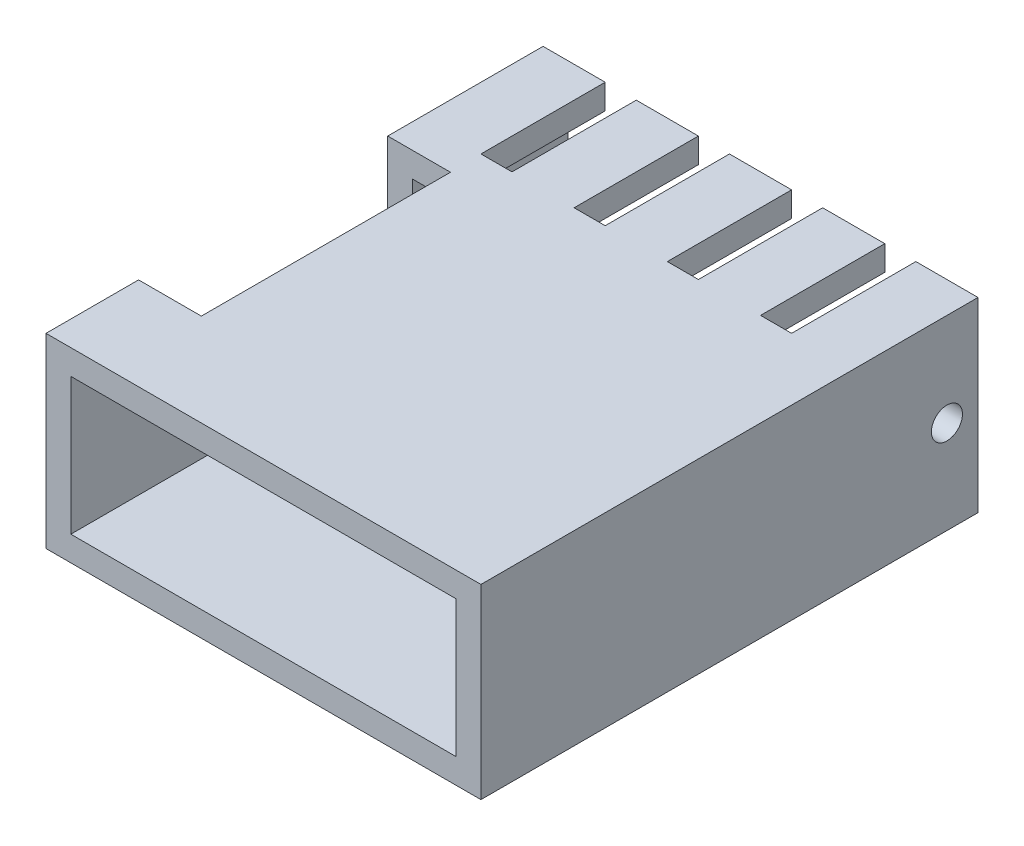
SolidWorks part; units mm, degrees
ref_plane "Front Plane" through (0, 0, 0) normal (0, 0, 1) x (1, 0, 0)
ref_plane "Top Plane" through (0, 0, 0) normal (0, 1, 0) x (1, 0, 0)
ref_plane "Right Plane" through (0, 0, 0) normal (1, 0, 0) x (0, 0, -1)
sketch "Sketch1" plane through (0, 0, 0) normal (0, 1, 0) x (1, 0, 0)
  line L1 (0, 0) -> (88.9, 0)
  line L2 (0, 0) -> (0, 101.6)
  line L3 (0, 101.6) -> (88.9, 101.6)
  line L4 (88.9, 0) -> (88.9, 101.6)
  dimension "D1" = 101.6
  dimension "D2" = 88.9
extrude "Boss-Extrude1" add sketch "Sketch1" along normal blind 38.1 contours L1 L4 L3 L2
shell "Shell1" thickness 5.08 removed face at (44.45, 19.05, -101.6) removed face at (44.45, 19.05, 0)
sketch "Sketch4" plane through (0, 0, 0) normal (0, -1, 0) x (1, 0, 0)
  line L0 (0, 0) -> (0, -101.6) construction
  line L1 (0, -18.923) -> (12.827, -18.923)
  line L2 (0, -18.923) -> (0, -69.85)
  line L3 (0, -69.85) -> (12.827, -69.85)
  line L4 (12.827, -18.923) -> (12.827, -69.85)
  line L5 (0, -101.6) -> (88.9, -101.6) construction
  point P5 (0, 0)
  point P10 (12.827, -25.273)
  dimension "D1" = 50.927
  dimension "D2" = 12.827
  dimension "D3" = 31.75
extrude "Cut-Extrude3" cut sketch "Sketch4" against normal through all from offset 19.05 offset against normal yes
sketch "Sketch5" plane through (0, 38.1, 0) normal (0, 1, 0) x (1, 0, 0)
  line L0 (0, 101.6) -> (88.9, 101.6) construction
  line L1 (12.7, 101.6) -> (19.05, 101.6)
  line L2 (12.7, 101.6) -> (12.7, 76.2)
  line L3 (12.7, 76.2) -> (19.05, 76.2)
  line L4 (19.05, 101.6) -> (19.05, 76.2)
  line L5 (31.75, 101.6) -> (31.75, 76.2)
  line L6 (31.75, 101.6) -> (38.1, 101.6)
  line L7 (38.1, 101.6) -> (38.1, 76.2)
  line L8 (31.75, 76.2) -> (38.1, 76.2)
  line L9 (50.8, 101.6) -> (50.8, 76.2)
  line L10 (50.8, 101.6) -> (57.15, 101.6)
  line L11 (57.15, 101.6) -> (57.15, 76.2)
  line L12 (50.8, 76.2) -> (57.15, 76.2)
  line L13 (69.85, 101.6) -> (69.85, 76.2)
  line L14 (69.85, 101.6) -> (76.2, 101.6)
  line L15 (76.2, 101.6) -> (76.2, 76.2)
  line L16 (69.85, 76.2) -> (76.2, 76.2)
  line L17 (12.7, 88.9) -> (76.2, 88.9) construction
  line L19 (12.7, 101.6) -> (5.08, 101.6) construction
  line L20 (0, 69.85) -> (0, 101.6) construction
  line L21 (76.2, 101.6) -> (83.82, 101.6) construction
  line L22 (88.9, 0) -> (88.9, 101.6) construction
  dimension "D1" = 25.4
  dimension "D2" = 6.35
  dimension "D4" = 5.08
  dimension "D5" = 5.08
  dimension "D6" = 63.5
  dimension "D3" = 4
extrude "Cut-Extrude4" cut sketch "Sketch5" against normal through all
sketch "Sketch6" plane through (0, 0, 0) normal (-1, 0, 0) x (0, 0, 1)
  line L0 (-101.6, 38.1) -> (-101.6, 0) construction
  circle A0 centre (-95.25, 19.05) radius 3.175
  point P4 (0, 0)
  point P5 (0, 0)
  point P6 (-101.6, 19.05)
  dimension "D1" = 6.35
  dimension "0.25" = 6.35
extrude "Cut-Extrude5" cut sketch "Sketch6" against normal through all and the other way blind 4.2672
